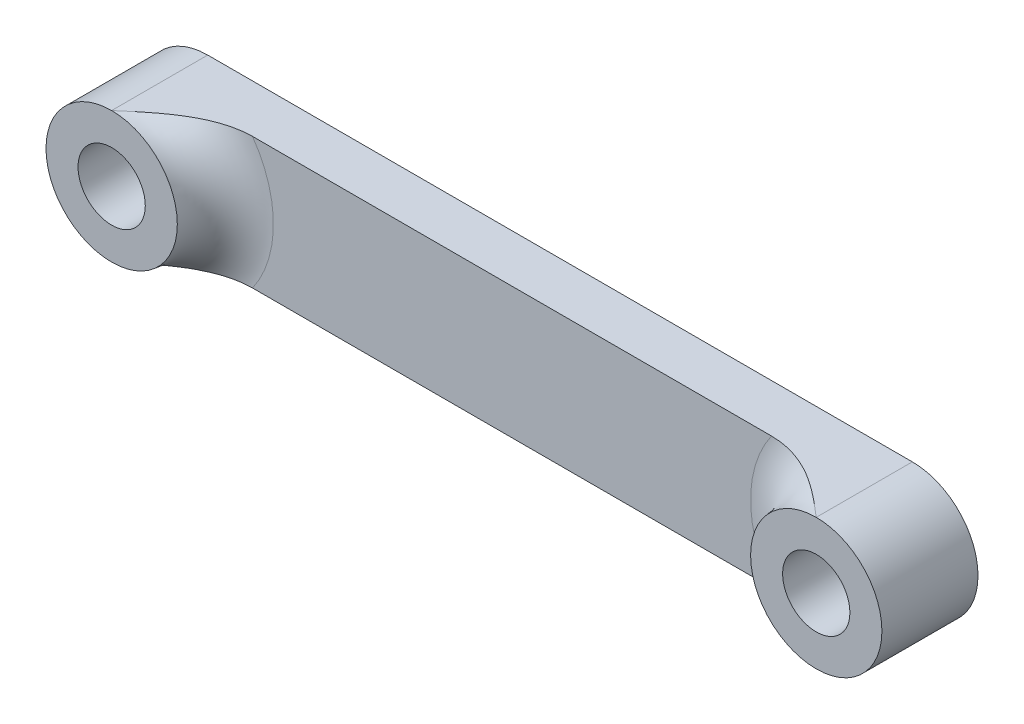
SolidWorks part; units mm, degrees
material "ABS"
ref_plane "Front Plane" through (0, 0, 0) normal (0, 0, 1) x (1, 0, 0)
ref_plane "Top Plane" through (0, 0, 0) normal (0, 1, 0) x (1, 0, 0)
ref_plane "Right Plane" through (0, 0, 0) normal (1, 0, 0) x (0, 0, -1)
sketch "Link Profile" plane through (0, 0, 0) normal (0, 0, 1) x (1, 0, 0)
  line L0 (0, 0) -> (44, 0) construction
  line L1 (0, 4.1) -> (44, 4.1)
  line L2 (0, -4.1) -> (44, -4.1)
  arc A0 (0, 4.1) -> (0, -4.1) centre (0, 0) ccw
  arc A1 (44, -4.1) -> (44, 4.1) centre (44, 0) ccw
  circle A2 centre (0, 0) radius 2.1
  circle A3 centre (44, 0) radius 2.1
  point P3 (22, 0)
  dimension "Hole Diameter" = 4.2
  dimension "Length" = 44
  dimension "Hole to Edge Distance" = 2
extrude "Link Extrude" add sketch "Link Profile" along normal blind 3
sketch "Sketch1" plane through (0, 0, 3) normal (0, 0, 1) x (1, 0, 0)
  circle A0 centre (0, 0) radius 4.1
  circle A1 centre (44, 0) radius 4.1
  circle A2 centre (44, 0) radius 2.1 construction
  circle A3 centre (0, 0) radius 2.1 construction
  circle A4 centre (44, 0) radius 2.1
  circle A5 centre (0, 0) radius 2.1
extrude "Boss-Extrude1" add sketch "Sketch1" along normal blind 3
fillet "Fillet1" radius 3 2 edges at (4.1, 0, 3) (39.9, 0, 3)
equation "\"Link Length\"= 44"
equation "\"Joint Hole Diameter\"= 4.2"
equation "\"Hole to Edge\"= 2"
equation "\"Link Thickness\"= 3"
equation "\"Length@Link Profile\" = \"Link Length\""
equation "\"Link Thickness@Link Extrude\" = \"Link Thickness\""
equation "\"Hole Diameter@Link Profile\" = \"Joint Hole Diameter\""
equation "\"Hole to Edge Distance@Link Profile\" = \"Hole to Edge\""
equation "\"Joint Extension\"= 3"
equation "\"D1@Boss-Extrude1\"=\"Joint Extension\""
equation "\"D1@Fillet1\"=\"Joint Extension\""
